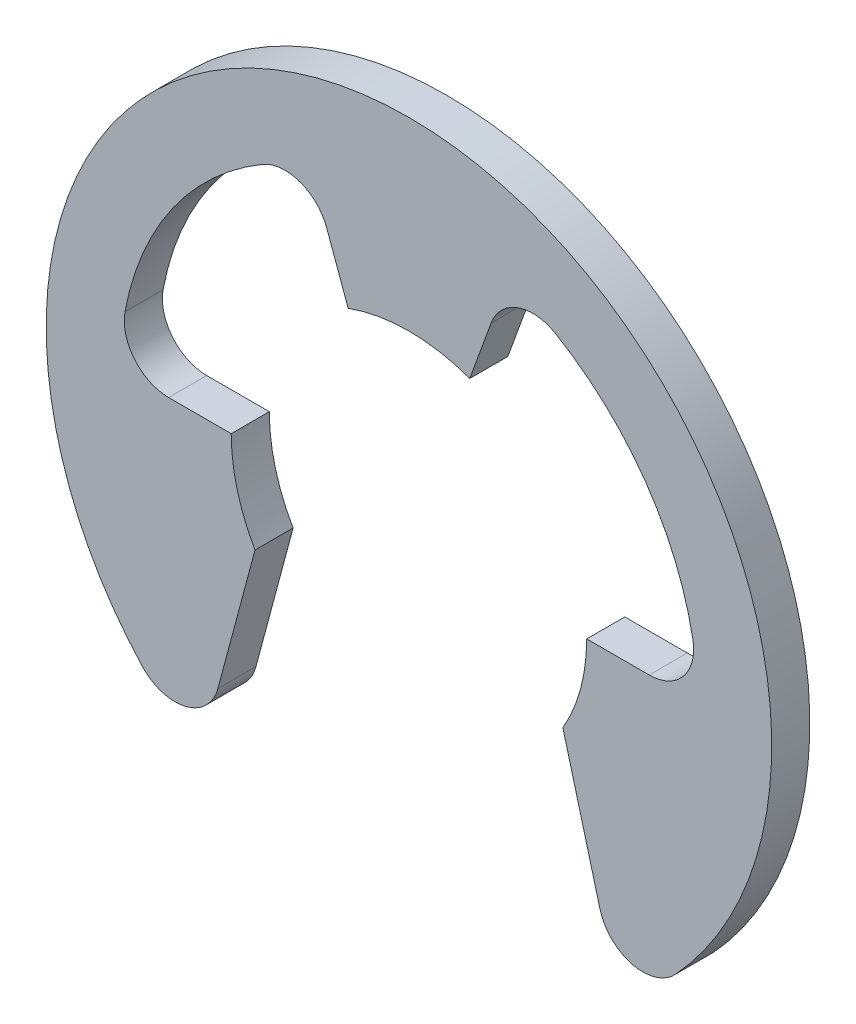
SolidWorks part; units mm, degrees
ref_plane "Plane1" through (0, 0, 0) normal (0, 0, 1) x (1, 0, 0)
ref_plane "Plane2" through (0, 0, 0) normal (0, 1, 0) x (1, 0, 0)
ref_plane "Plane3" through (0, 0, 0) normal (1, 0, 0) x (0, 0, -1)
sketch "Clipboard" plane through (0, 0, 0) normal (0, 0, 1) x (1, 0, 0)
  circle A0 centre (0, 0) radius 4.9784
  circle A1 centre (0, 0) radius 10.16
sketch "BodySke" plane through (0, 0, 0) normal (0, 0, 1) x (1, 0, 0)
  line L0 (0, 0) -> (1.7027, 4.6782) construction
  line L1 (0, 0) -> (-1.7027, 4.6782) construction
  line L2 (0, 0.6037) -> (0, -0.6192) construction
  line L3 (0, 0) -> (1.2813, -0.7398) construction
  line L4 (0, 0) -> (-1.295, -0.7477) construction
  line L5 (0, 0) -> (4.9784, 0) construction
  line L6 (0, 0) -> (-4.9784, 0) construction
  line L7 (4.3114, -2.4892) -> (5.3511, -6.3692)
  line L8 (-4.3114, -2.4892) -> (-5.3511, -6.3692)
  line L9 (4.9784, 0) -> (6.7298, 0)
  line L10 (-4.9784, 0) -> (-6.7298, 0)
  line L11 (-1.7027, 4.6782) -> (-2.3017, 6.324)
  line L12 (1.7027, 4.6782) -> (2.3017, 6.324)
  arc A0 (-4.9784, 0) -> (-4.3114, -2.4892) centre (0, 0) ccw
  arc A1 (7.4661, -6.8908) -> (-7.4661, -6.8908) centre (0, 0) ccw
  arc A2 (-4.1009, 6.9705) -> (-7.9527, 1.4696) centre (0, 0) ccw
  arc A3 (7.9527, 1.4696) -> (4.1009, 6.9705) centre (0, 0) ccw
  circle A4 centre (0, 0) radius 10.16 construction
  arc A5 (1.7027, 4.6782) -> (-1.7027, 4.6782) centre (0, 0) ccw
  arc A6 (4.3114, -2.4892) -> (4.9784, 0) centre (0, 0) ccw
  circle A7 centre (0, 0) radius 4.9784 construction
  arc A8 (5.3511, -6.3692) -> (7.4661, -6.8908) centre (6.5523, -6.0473) ccw
  arc A9 (-5.3511, -6.3692) -> (-7.4661, -6.8908) centre (-6.5523, -6.0473) cw
  arc A10 (-6.7298, 0) -> (-7.9527, 1.4696) centre (-6.7298, 1.2436) cw
  arc A11 (-2.3017, 6.324) -> (-4.1009, 6.9705) centre (-3.4703, 5.8987) ccw
  arc A12 (2.3017, 6.324) -> (4.1009, 6.9705) centre (3.4703, 5.8987) cw
  arc A13 (6.7298, 0) -> (7.9527, 1.4696) centre (6.7298, 1.2436) ccw
  point P28 (-8.0874, 0)
  point P36 (8.0874, 0)
  dimension "D3" = 1.2436
  dimension "D5" = 8.0874
  dimension "D1" = 40
  dimension "D2" = 30
  dimension "D4" = 15
extrude "Body" add sketch "BodySke" against normal blind 1.0668
equation "\"D5@BodySke\" =  ( 3 / 5 * \"FreeOutsideDia@Clipboard\" + 2 / 5 * \"FreeDia@Clipboard\" )  / 2"
equation "\"D3@BodySke\" =  ( \"D5@BodySke\" * 2 - \"FreeDia@Clipboard\" )  / 2 / 2.5"
